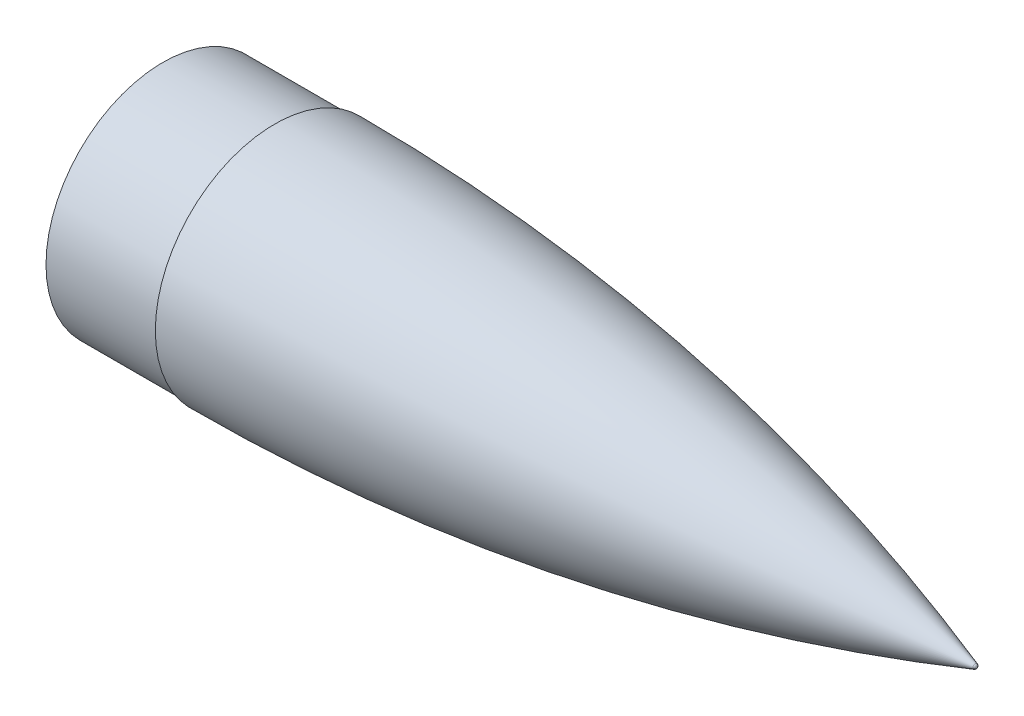
SolidWorks part; units mm, degrees
ref_plane "前基準面" through (0, 0, 0) normal (0, 0, 1) x (1, 0, 0)
ref_plane "上基準面" through (0, 0, 0) normal (0, 1, 0) x (1, 0, 0)
ref_plane "右基準面" through (0, 0, 0) normal (1, 0, 0) x (0, 0, -1)
sketch "草圖2" plane through (0, 0, 0) normal (0, 0, 1) x (1, 0, 0)
  line L0 (-558.8, 95) -> (-558.8, 94)
  line L1 (0, 0) -> (-3.5404, 0)
  line L3 (-711, 0) -> (126.4299, 0) construction
  line L4 (0, 26.965) -> (0, -35.3928) construction
  line L5 (-558.8, 95) -> (-39.4127, 95) construction
  line L7 (-647.8, 91) -> (-558.8, 91)
  line L8 (-647.8, 91) -> (-647.8, 93)
  line L9 (-647.8, 93) -> (-559.8, 93)
  line L10 (-558.8, 91) -> (-558.8, 91.4997)
  line L11 (-647.8, 91) -> (-558.8, 93) construction
  line L12 (-647.8, 93) -> (-558.8, 91) construction
  arc A1 (0, 0) -> (-1.35, 1.8914) centre (-2, 0) ccw
  arc A2 (-1.35, 1.8914) -> (-558.8, 95) centre (-558.8, -1620.3077) ccw
  arc A3 (-3.5404, 0) -> (-557.7994, 92.4997) centre (-558.8, -1620.3077) ccw
  arc A4 (-558.8, 94) -> (-559.8, 93) centre (-559.8, 94) cw
  arc A5 (-2.1625, -0.4729) -> (-558.8, 92.5) centre (-558.8, -1620.3077) ccw construction
  arc A6 (-557.7994, 92.4997) -> (-558.8, 91.4997) centre (-557.8, 91.4997) ccw
  point P4 (-603.3, 92)
  dimension "D3" = 2
  dimension "D5" = 1
  dimension "D9" = 1
  dimension "D1" = 95
  dimension "D2" = 558.8
  dimension "D6" = 89
  dimension "D7" = 186
  dimension "D8" = 182
  dimension "D4" = 2.5
revolve "旋轉1" add sketch "草圖2" angle 360 about L3 region at (-276.3217, 70.917, 0)
